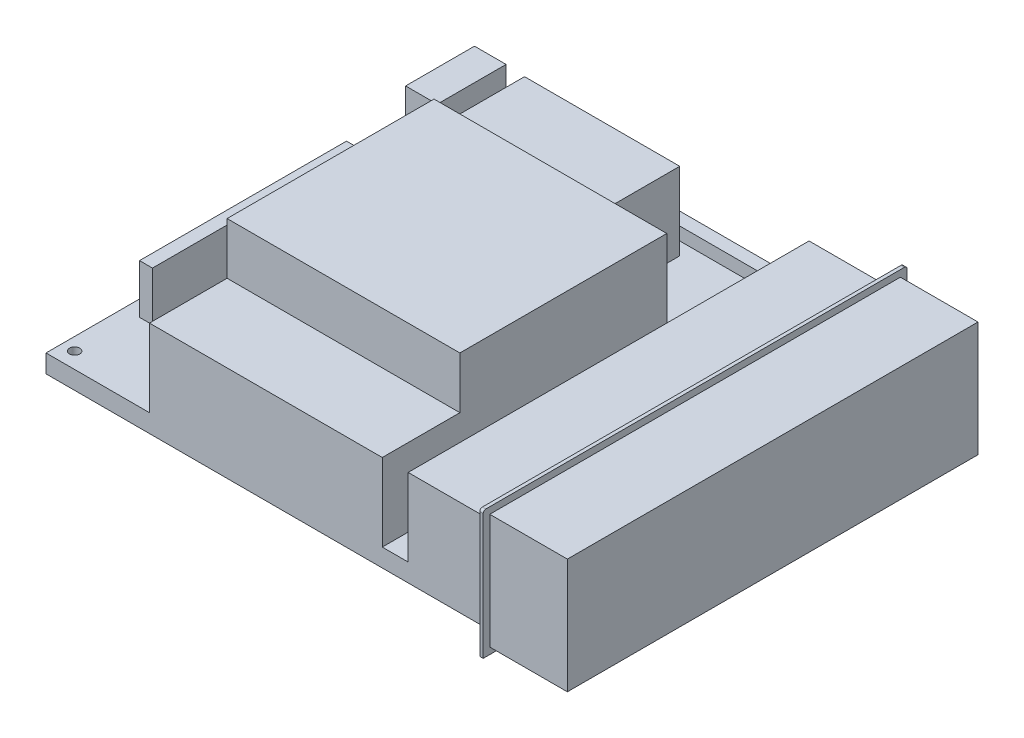
SolidWorks part; units mm, degrees
ref_plane "Front Plane" through (0, 0, 0) normal (0, 0, 1) x (1, 0, 0)
ref_plane "Top Plane" through (0, 0, 0) normal (0, 1, 0) x (1, 0, 0)
ref_plane "Right Plane" through (0, 0, 0) normal (1, 0, 0) x (0, 0, -1)
sketch "Sketch1" plane through (0, 0, 0) normal (0, 1, 0) x (1, 0, 0)
  line L1 (-85, -85) -> (85, -85)
  line L2 (-85, -85) -> (-85, 85)
  line L3 (-85, 85) -> (85, 85)
  line L4 (85, -85) -> (85, 85)
  line L5 (-85, -85) -> (85, 85) construction
  line L6 (-85, 85) -> (85, -85) construction
  point P0 (0, 0)
  dimension "D1" = 170
extrude "alusplaat" add sketch "Sketch1" along normal blind 2
sketch "Sketch2" plane through (0, 2, 0) normal (0, 1, 0) x (-1, 0, 0)
  line L1 (-85, 85) -> (-55, 85)
  line L2 (-85, 85) -> (-85, -70)
  line L3 (-85, -70) -> (-55, -70)
  line L4 (-55, 85) -> (-55, -70)
  dimension "D1" = 155
  dimension "D2" = 30
extrude "pistikud" add sketch "Sketch2" along normal blind 35
sketch "Sketch3" plane through (0, 2, 0) normal (0, 1, 0) x (1, 0, 0)
  line L0 (-85, -85) -> (55, -85) construction
  line L1 (-45, -85) -> (45, -85)
  line L2 (-45, -85) -> (-45, 25)
  line L3 (-45, 25) -> (45, 25)
  line L4 (45, -85) -> (45, 25)
  line L5 (-85, 85) -> (-85, -85) construction
  dimension "D1" = 90
  dimension "D2" = 40
  dimension "D3" = 110
extrude "cpu+mälud" add sketch "Sketch3" along normal blind 55
sketch "Sketch4" plane through (0, 2, 0) normal (0, 1, 0) x (1, 0, 0)
  line L1 (5, 35) -> (-55, 35)
  line L2 (5, 35) -> (5, 70)
  line L3 (5, 70) -> (-55, 70)
  line L4 (-55, 35) -> (-55, 70)
  line L5 (-85, 85) -> (-85, -85) construction
  line L6 (85, 85) -> (-85, 85) construction
  dimension "D1" = 35
  dimension "D2" = 60
  dimension "D3" = 30
  dimension "D4" = 15
extrude "sinine radikas" add sketch "Sketch4" along normal blind 35
sketch "Sketch5" plane through (0, 2, 0) normal (0, 1, 0) x (-1, 0, 0)
  line L0 (85, -85) -> (85, 85) construction
  line L1 (45, -75) -> (-45, -75)
  line L2 (45, -75) -> (45, -80)
  line L3 (45, -80) -> (-45, -80)
  line L4 (-45, -75) -> (-45, -80)
  line L5 (-85, -85) -> (85, -85) construction
  dimension "D1" = 90
  dimension "D2" = 40
  dimension "D3" = 5
  dimension "D4" = 5
extrude "pcie pesa" add sketch "Sketch5" along normal blind 10
sketch "Sketch6" plane through (0, 2, 0) normal (0, 1, 0) x (-1, 0, 0)
  line L1 (67.672, -48.9124) -> (79.8888, -48.9124)
  line L2 (67.672, -48.9124) -> (67.672, -75.5395)
  line L3 (67.672, -75.5395) -> (79.8888, -75.5395)
  line L4 (79.8888, -48.9124) -> (79.8888, -75.5395)
extrude "raid pesad" add sketch "Sketch6" along normal blind 30
sketch "Sketch7" plane through (0, 2, 0) normal (0, 1, 0) x (-1, 0, 0)
  line L1 (85, -85) -> (-85, -85)
  line L2 (85, -85) -> (85, 85)
  line L3 (85, 85) -> (-85, 85)
  line L4 (-85, -85) -> (-85, 85)
extrude "üleüldine müra" add sketch "Sketch7" along normal blind 5
sketch "Sketch8" plane through (0, 7, 0) normal (0, 1, 0) x (-1, 0, 0)
  line L0 (-85, -85) -> (85, -85) construction
  line L1 (78.8401, -25) -> (73.8401, -25)
  line L2 (78.8401, -25) -> (78.8401, 55)
  line L3 (78.8401, 55) -> (73.8401, 55)
  line L4 (73.8401, -25) -> (73.8401, 55)
  dimension "D1" = 5
  dimension "D2" = 80
  dimension "D3" = 60
extrude "patrei ja igasugused lülitid" add sketch "Sketch8" along normal blind 19
sketch "Sketch9" plane through (0, 57, 0) normal (0, 1, 0) x (-1, 0, 0)
  line L0 (-45, 85) -> (-45, -25) construction
  line L1 (45, -25) -> (-45, -25)
  line L2 (45, -25) -> (45, 55)
  line L3 (45, 55) -> (-45, 55)
  line L4 (-45, -25) -> (-45, 55)
  dimension "D1" = 80
extrude "mälud" cut sketch "Sketch9" against normal blind 20 flip side to cut
sketch "Sketch10" plane through (0, 7, 0) normal (0, 1, 0) x (1, 0, 0)
  line L0 (85, 85) -> (-85, 85) construction
  line L1 (74.84, 78.65) -> (-80.1, 78.65) construction
  line L2 (74.84, 78.65) -> (74.84, -78.83) construction
  line L3 (74.84, -78.83) -> (-80.1, -78.83) construction
  line L4 (-80.1, 78.65) -> (-80.1, -78.83) construction
  line L5 (85, 70) -> (85, 85) construction
  circle A0 centre (74.84, 78.65) radius 1.98
  circle A1 centre (-80.1, 78.65) radius 1.98
  circle A2 centre (-80.1, -78.83) radius 1.98
  circle A3 centre (51.98, -78.83) radius 1.98
  dimension "D6" = 3.96
  dimension "D1" = 6.35
  dimension "D2" = 10.16
  dimension "D3" = 154.94
  dimension "D4" = 157.48
  dimension "D5" = 22.86
extrude "Cut-Extrude2" cut sketch "Sketch10" against normal up to next
sketch "Sketch13" plane through (0, 7, 0) normal (0, 1, 0) x (1, 0, 0)
  line L1 (74.84, 78.65) -> (87.11, 78.65)
  line L2 (74.84, 78.65) -> (74.84, -92.9265)
  line L3 (74.84, -92.9265) -> (87.11, -92.9265)
  line L4 (87.11, 78.65) -> (87.11, -92.9265)
  dimension "D1" = 12.27
ref_plane "Plane2" through (87.11, 0, 0) normal (1, 0, 0) x (0, 0, -1)
sketch "Sketch11" plane through (87.11, 0, 0) normal (1, 0, 0) x (0, 0, -1)
  line L0 (-85, 0) -> (85, 0) construction
  line L1 (-86.875, -3.81) -> (71.875, -3.81) construction
  line L2 (-86.875, -3.81) -> (-86.875, 40.64) construction
  line L3 (-86.875, 40.64) -> (71.875, 40.64) construction
  line L4 (71.875, -3.81) -> (71.875, 40.64) construction
  line L5 (-88.415, 43.18) -> (73.415, 43.18)
  line L6 (71.875, 18.415) -> (70, 18.415) construction
  line L7 (70, 37) -> (70, 7) construction
  line L8 (-86.875, 18.415) -> (-85, 18.415) construction
  line L9 (-85, 37) -> (-85, 0) construction
  line L10 (74.415, -5.35) -> (74.415, 42.18)
  line L11 (-89.415, -6.35) -> (73.415, -6.35)
  line L12 (-89.415, -6.35) -> (-89.415, 42.18)
  line L13 (-89.415, -6.35) -> (74.415, -6.35) construction
  line L14 (74.415, -6.35) -> (74.415, 43.18) construction
  line L15 (-89.415, 43.18) -> (74.415, 43.18) construction
  line L16 (-89.415, -6.35) -> (-89.415, 43.18) construction
  arc A0 (73.415, -6.35) -> (74.415, -5.35) centre (73.415, -5.35) ccw
  arc A1 (74.415, 42.18) -> (73.415, 43.18) centre (73.415, 42.18) ccw
  arc A2 (-88.415, 43.18) -> (-89.415, 42.18) centre (-88.415, 42.18) ccw
  dimension "D5" = 1
  dimension "D1" = 158.75
  dimension "D2" = 44.45
  dimension "D3" = 3.81
  dimension "D4" = 2.54
extrude "Boss-Extrude1" add sketch "Sketch11" along normal blind 1.32
sketch "Sketch12" plane through (88.43, 0, 0) normal (1, 0, 0) x (0, 0, -1)
  line L1 (-86.875, -3.81) -> (71.875, -3.81)
  line L2 (-86.875, -3.81) -> (-86.875, 40.64)
  line L3 (-86.875, 40.64) -> (71.875, 40.64)
  line L4 (71.875, -3.81) -> (71.875, 40.64)
  line L5 (-88.415, 43.18) -> (73.415, 43.18)
  line L10 (74.415, -5.35) -> (74.415, 42.18)
  line L11 (-89.415, -6.35) -> (73.415, -6.35)
  line L12 (-89.415, -6.35) -> (-89.415, 42.18)
  line L13 (-89.415, -6.35) -> (74.415, -6.35) construction
  line L14 (74.415, -6.35) -> (74.415, 43.18) construction
  line L15 (-89.415, 43.18) -> (74.415, 43.18) construction
  line L16 (-89.415, -6.35) -> (-89.415, 43.18) construction
  arc A0 (73.415, -6.35) -> (74.415, -5.35) centre (73.415, -5.35) ccw
  arc A1 (74.415, 42.18) -> (73.415, 43.18) centre (73.415, 42.18) ccw
  arc A2 (-88.415, 43.18) -> (-89.415, 42.18) centre (-88.415, 42.18) ccw
  arc A5 (-88.415, 43.18) -> (-89.415, 42.18) centre (-88.415, 42.18) ccw construction
  dimension "D5" = 1
  dimension "D1" = 158.75
  dimension "D2" = 44.45
  dimension "D4" = 2.54
extrude "Boss-Extrude2" add sketch "Sketch12" along normal blind 30 contours L1 L4 L3 L2 region at (88.43, 18.415, 7.5)
